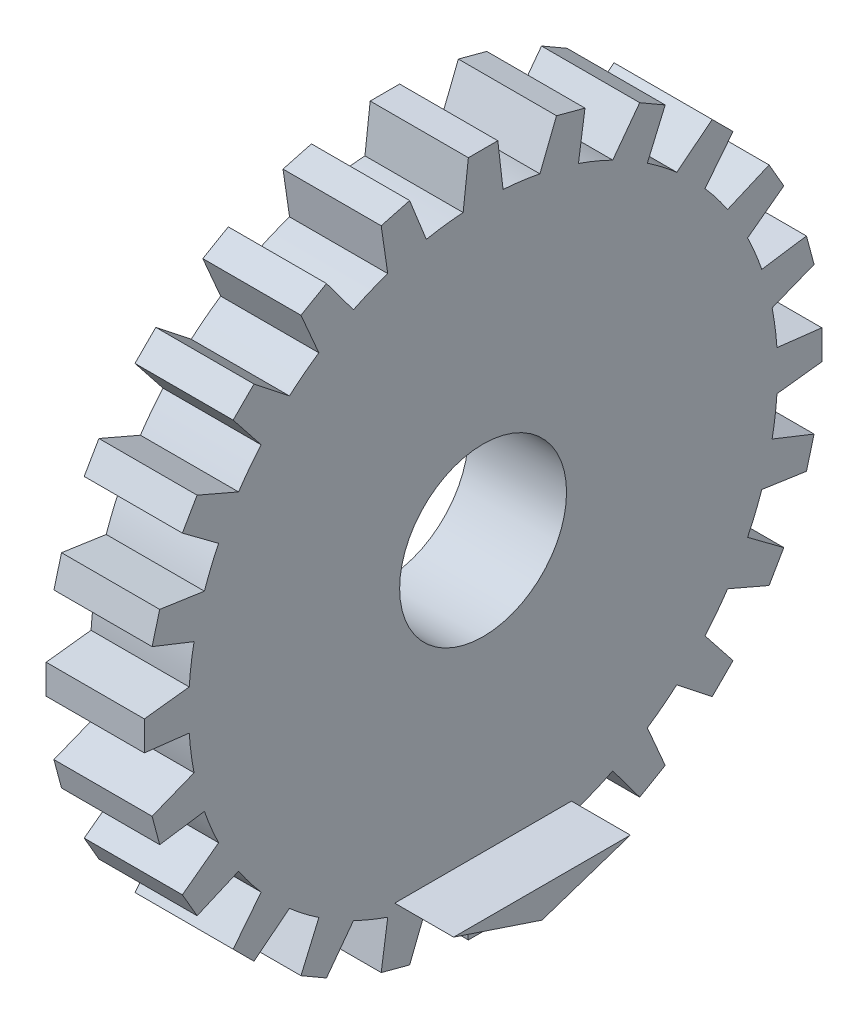
SolidWorks part; units mm, degrees
ref_plane "Front Plane" through (0, 0, 0) normal (0, 0, 1) x (1, 0, 0)
ref_plane "Top Plane" through (0, 0, 0) normal (0, 1, 0) x (1, 0, 0)
ref_plane "Right Plane" through (0, 0, 0) normal (1, 0, 0) x (0, 0, -1)
sketch "Sketch2" plane through (0, 0, 0) normal (1, 0, 0) x (0, 0, -1)
  circle A0 centre (0, 0) radius 5
  dimension "D1" = 10
extrude "Boss-Extrude1" add sketch "Sketch2" along normal blind 100
sketch "Sketch4" plane through (0, 0, 0) normal (-1, 0, 0) x (0, 0, 1)
  circle A0 centre (0, 0) radius 5
  point P1 (0, 0)
sketch "Sketch5" plane through (100, 0, 0) normal (1, 0, 0) x (0, 0, -1)
  point P0 (0, 0)
sketch "Sketch6" plane through (0, 0, 0) normal (0, 1, 0) x (1, 0, 0)
  line L0 (0, 0) -> (100, 0) construction
  point P4 (30, 0)
  dimension "D1" = 30
ref_plane "Plane1" through (30, 0, 0) normal (-1, 0, 0) x (0, 0, 1)
sketch "Sketch7" plane through (30, 0, 0) normal (-1, 0, 0) x (0, 0, 1)
  circle A0 centre (0, 0) radius 7
  dimension "D1" = 14
extrude "Boss-Extrude2" [suppressed] add sketch "Sketch7" along normal blind 5
sketch "Sketch8" plane through (0, 0, 0) normal (-1, 0, 0) x (0, 0, 1)
  line L0 (0, 30) -> (0, -30) construction
  line L1 (0, 30) -> (0, 34.5)
  line L2 (0, 34.5) -> (1.5, 34.5)
  line L3 (1.5, 34.5) -> (2.0333, 29.931)
  line L4 (0, 34.5) -> (-1.5, 34.5)
  line L5 (-1.5, 34.5) -> (-2.0333, 29.931)
  line L6 (7.4804, 33.7127) -> (5.7827, 29.4374)
  line L7 (8.9293, 33.3244) -> (7.4804, 33.7127)
  line L8 (8.9293, 33.3244) -> (10.3781, 32.9362)
  line L9 (10.3781, 32.9362) -> (9.7107, 28.3849)
  line L10 (15.951, 30.6279) -> (13.2046, 26.9377)
  line L11 (17.25, 29.8779) -> (15.951, 30.6279)
  line L12 (17.25, 29.8779) -> (18.549, 29.1279)
  line L13 (18.549, 29.1279) -> (16.7264, 24.9044)
  line L14 (23.3345, 25.4558) -> (19.7267, 22.6022)
  line L15 (24.3952, 24.3952) -> (23.3345, 25.4558)
  line L16 (24.3952, 24.3952) -> (25.4558, 23.3345)
  line L17 (25.4558, 23.3345) -> (22.6022, 19.7267)
  line L18 (29.1279, 18.549) -> (24.9044, 16.7264)
  line L19 (29.8779, 17.25) -> (29.1279, 18.549)
  line L20 (29.8779, 17.25) -> (30.6279, 15.951)
  line L21 (30.6279, 15.951) -> (26.9377, 13.2046)
  line L22 (32.9362, 10.3781) -> (28.3849, 9.7107)
  line L23 (33.3244, 8.9293) -> (32.9362, 10.3781)
  line L24 (33.3244, 8.9293) -> (33.7127, 7.4804)
  line L25 (33.7127, 7.4804) -> (29.4374, 5.7827)
  line L26 (34.5, 1.5) -> (29.931, 2.0333)
  line L27 (34.5, 0) -> (34.5, 1.5)
  line L28 (34.5, 0) -> (34.5, -1.5)
  line L29 (34.5, -1.5) -> (29.931, -2.0333)
  line L30 (33.7127, -7.4804) -> (29.4374, -5.7827)
  line L31 (33.3244, -8.9293) -> (33.7127, -7.4804)
  line L32 (33.3244, -8.9293) -> (32.9362, -10.3781)
  line L33 (32.9362, -10.3781) -> (28.3849, -9.7107)
  line L34 (30.6279, -15.951) -> (26.9377, -13.2046)
  line L35 (29.8779, -17.25) -> (30.6279, -15.951)
  line L36 (29.8779, -17.25) -> (29.1279, -18.549)
  line L37 (29.1279, -18.549) -> (24.9044, -16.7264)
  line L38 (25.4558, -23.3345) -> (22.6022, -19.7267)
  line L39 (24.3952, -24.3952) -> (25.4558, -23.3345)
  line L40 (24.3952, -24.3952) -> (23.3345, -25.4558)
  line L41 (23.3345, -25.4558) -> (19.7267, -22.6022)
  line L42 (18.549, -29.1279) -> (16.7264, -24.9044)
  line L43 (17.25, -29.8779) -> (18.549, -29.1279)
  line L44 (17.25, -29.8779) -> (15.951, -30.6279)
  line L45 (15.951, -30.6279) -> (13.2046, -26.9377)
  line L46 (10.3781, -32.9362) -> (9.7107, -28.3849)
  line L47 (8.9293, -33.3244) -> (10.3781, -32.9362)
  line L48 (8.9293, -33.3244) -> (7.4804, -33.7127)
  line L49 (7.4804, -33.7127) -> (5.7827, -29.4374)
  line L50 (1.5, -34.5) -> (2.0333, -29.931)
  line L51 (0, -34.5) -> (1.5, -34.5)
  line L52 (0, -34.5) -> (-1.5, -34.5)
  line L53 (-1.5, -34.5) -> (-2.0333, -29.931)
  line L54 (-7.4804, -33.7127) -> (-5.7827, -29.4374)
  line L55 (-8.9293, -33.3244) -> (-7.4804, -33.7127)
  line L56 (-8.9293, -33.3244) -> (-10.3781, -32.9362)
  line L57 (-10.3781, -32.9362) -> (-9.7107, -28.3849)
  line L58 (-15.951, -30.6279) -> (-13.2046, -26.9377)
  line L59 (-17.25, -29.8779) -> (-15.951, -30.6279)
  line L60 (-17.25, -29.8779) -> (-18.549, -29.1279)
  line L61 (-18.549, -29.1279) -> (-16.7264, -24.9044)
  line L62 (-23.3345, -25.4558) -> (-19.7267, -22.6022)
  line L63 (-24.3952, -24.3952) -> (-23.3345, -25.4558)
  line L64 (-24.3952, -24.3952) -> (-25.4558, -23.3345)
  line L65 (-25.4558, -23.3345) -> (-22.6022, -19.7267)
  line L66 (-29.1279, -18.549) -> (-24.9044, -16.7264)
  line L67 (-29.8779, -17.25) -> (-29.1279, -18.549)
  line L68 (-29.8779, -17.25) -> (-30.6279, -15.951)
  line L69 (-30.6279, -15.951) -> (-26.9377, -13.2046)
  line L70 (-32.9362, -10.3781) -> (-28.3849, -9.7107)
  line L71 (-33.3244, -8.9293) -> (-32.9362, -10.3781)
  line L72 (-33.3244, -8.9293) -> (-33.7127, -7.4804)
  line L73 (-33.7127, -7.4804) -> (-29.4374, -5.7827)
  line L74 (-34.5, -1.5) -> (-29.931, -2.0333)
  line L75 (-34.5, 0) -> (-34.5, -1.5)
  line L76 (-34.5, 0) -> (-34.5, 1.5)
  line L77 (-34.5, 1.5) -> (-29.931, 2.0333)
  line L78 (-33.7127, 7.4804) -> (-29.4374, 5.7827)
  line L79 (-33.3244, 8.9293) -> (-33.7127, 7.4804)
  line L80 (-33.3244, 8.9293) -> (-32.9362, 10.3781)
  line L81 (-32.9362, 10.3781) -> (-28.3849, 9.7107)
  line L82 (-30.6279, 15.951) -> (-26.9377, 13.2046)
  line L83 (-29.8779, 17.25) -> (-30.6279, 15.951)
  line L84 (-29.8779, 17.25) -> (-29.1279, 18.549)
  line L85 (-29.1279, 18.549) -> (-24.9044, 16.7264)
  line L86 (-25.4558, 23.3345) -> (-22.6022, 19.7267)
  line L87 (-24.3952, 24.3952) -> (-25.4558, 23.3345)
  line L88 (-24.3952, 24.3952) -> (-23.3345, 25.4558)
  line L89 (-23.3345, 25.4558) -> (-19.7267, 22.6022)
  line L90 (-18.549, 29.1279) -> (-16.7264, 24.9044)
  line L91 (-17.25, 29.8779) -> (-18.549, 29.1279)
  line L92 (-17.25, 29.8779) -> (-15.951, 30.6279)
  line L93 (-15.951, 30.6279) -> (-13.2046, 26.9377)
  line L94 (-10.3781, 32.9362) -> (-9.7107, 28.3849)
  line L95 (-8.9293, 33.3244) -> (-10.3781, 32.9362)
  line L96 (-8.9293, 33.3244) -> (-7.4804, 33.7127)
  line L97 (-7.4804, 33.7127) -> (-5.7827, 29.4374)
  circle A1 centre (0, 0) radius 30
  point P127 (0, 0)
  circle M6 centre (0, 0) radius 5
  dimension "D1" = 60
  dimension "D2" = 4.5
  dimension "D3" = 1.5
  dimension "D4" = 3
  dimension "D5" = 4.6
  dimension "D6" = 4.6
extrude "Boss-Extrude3" add sketch "Sketch8" against normal blind 10 contours L0 A1 M6 | A1 L0 M6 | A1 L97 L96 L95 L94 | A1 L9 L8 L7 L6 | A1 L13 L12 L11 L10 | A1 L17 L16 L15 L14 | A1 L21 L20 L19 L18 | A1 L25 L24 L23 L22 | A1 L29 L28 L27 L26 | A1 L33 L32 L31 L30 | A1 L93 L92 L91 L90 | A1 L89 L88 L87 L86 | A1 L85 L84 L83 L82 | A1 L81 L80 L79 L78 | A1 L77 L76 L75 L74 | A1 L73 L72 L71 L70 | A1 L69 L68 L67 L66 | A1 L65 L64 L63 L62 | A1 L61 L60 L59 L58 | A1 L57 L56 L55 L54 | A1 L53 L52 L51 L50 | A1 L49 L48 L47 L46 | A1 L45 L44 L43 L42 | A1 L41 L40 L39 L38 | A1 L37 L36 L35 L34 | A1 L1 L4 L5 | A1 L3 L2 L1 region at (0, 0, 13.0355) region at (0, 32.1257, -0.8915) region at (0, 32.1257, 0.8915) region at (0, 0, -13.0355) region at (0, 31.031, 8.3147) region at (0, 31.031, -8.3147) region at (0, -32.1257, 0) region at (0, 27.8217, 16.0628) region at (0, 27.8217, -16.0628) region at (0, -31.031, -8.3147) region at (0, -31.031, 8.3147) region at (0, 22.7163, 22.7163) region at (0, 22.7163, -22.7163) region at (0, -27.8217, -16.0628) region at (0, -27.8217, 16.0628) region at (0, 16.0628, 27.8217) region at (0, 16.0628, -27.8217) region at (0, -22.7163, -22.7163) region at (0, -22.7163, 22.7163) region at (0, 8.3147, 31.031) region at (0, 8.3147, -31.031) region at (0, -16.0628, -27.8217) region at (0, -16.0628, 27.8217) region at (0, 0, 32.1257) region at (0, 0, -32.1257) region at (0, -8.3147, -31.031) region at (0, -8.3147, 31.031)
sketch "Sketch9" plane through (100, 0, 0) normal (1, 0, 0) x (0, 0, -1)
  circle A0 centre (0, 0) radius 5
  dimension "D1" = 10
extrude "Boss-Extrude4" add sketch "Sketch9" along normal blind 100
extrude "Boss-Extrude5" add sketch "Sketch4" along normal blind 100
ref_plane "Plane2" through (0, 5, 0) normal (0, 1, 0) x (1, 0, 0)
sketch "Sketch12" plane through (-100, 0, 0) normal (-1, 0, 0) x (0, 0, 1)
  line L0 (-5, 0) -> (-5, 5) construction
  line L1 (21.725, 5) -> (-21.725, 5) construction
  line L2 (5, 0) -> (5, 5) construction
  circle A0 centre (0, 0) radius 5 construction
  circle A1 centre (0, 0) radius 5 construction
sketch "Sketch13" plane through (0, 5, 0) normal (0, 1, 0) x (1, 0, 0)
  line L0 (-100, -5) -> (0, -5) construction
  line L1 (-100, 5) -> (-90, 5)
  line L2 (-100, 5) -> (-100, -5)
  line L3 (-100, -5) -> (-90, -5)
  line L4 (-90, 5) -> (-90, -5)
  dimension "D1" = 10
extrude "Boss-Extrude6" [suppressed] add sketch "Sketch13" along normal blind 40 and the other way blind 5
sketch "Sketch15" plane through (200, 0, 0) normal (1, 0, 0) x (0, 0, -1)
  line L0 (-5, 0) -> (-5, 5) construction
  line L1 (5, 0) -> (5, 5) construction
sketch "Sketch16" plane through (0, 5, 0) normal (0, 1, 0) x (1, 0, 0)
  line L0 (10, -5) -> (200, -5) construction
  line L1 (200, 5) -> (190, 5)
  line L2 (200, 5) -> (200, -5)
  line L3 (200, -5) -> (190, -5)
  line L4 (190, 5) -> (190, -5)
  dimension "D1" = 10
extrude "Boss-Extrude7" [suppressed] add sketch "Sketch16" along normal blind 40 and the other way blind 5
sketch "Sketch17" plane through (200, 0, 0) normal (1, 0, 0) x (0, 0, -1)
  circle A0 centre (0, 0) radius 8.5
  dimension "D1" = 17
extrude "Cut-Extrude1" cut sketch "Sketch17" against normal blind 305
sketch "Sketch18" plane through (10, 0, 0) normal (1, 0, 0) x (0, 0, -1)
  line L0 (0, -30.5) -> (9, -27.5)
  line L1 (9, -27.5) -> (-9, -27.5)
  line L2 (-9, -27.5) -> (0, -30.5)
  line L3 (-1.5, -34.5) -> (1.5, -34.5) construction
  dimension "D1" = 9
  dimension "D2" = 9
  dimension "D3" = 4
  dimension "D4" = 1.5
  dimension "D5" = 3
extrude "Boss-Extrude8" add sketch "Sketch18" along normal blind 6
